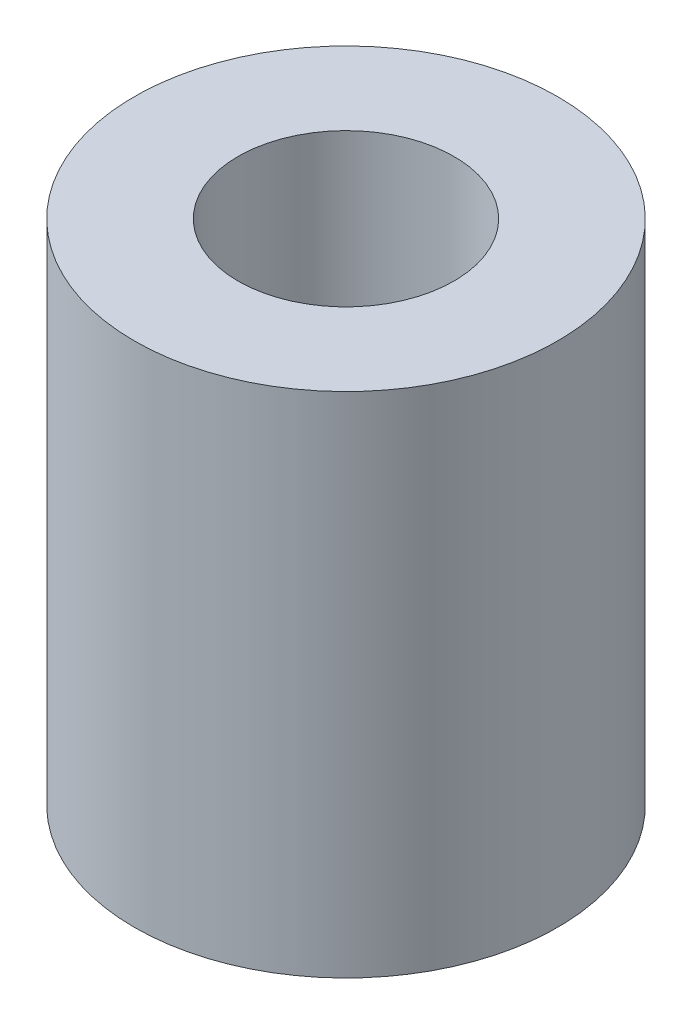
SolidWorks part; units mm, degrees
ref_plane "Front Plane" through (0, 0, 0) normal (0, 0, 1) x (1, 0, 0)
ref_plane "Top Plane" through (0, 0, 0) normal (0, 1, 0) x (1, 0, 0)
ref_plane "Right Plane" through (0, 0, 0) normal (1, 0, 0) x (0, 0, -1)
sketch "Sketch1" plane through (0, 0, 0) normal (0, 1, 0) x (1, 0, 0)
  circle A0 centre (0, 0) radius 7.9375
  dimension "D1" = 15.875
extrude "Boss-Extrude1" add sketch "Sketch1" along normal blind 19.05
sketch "Sketch2" plane through (0, 19.05, 0) normal (0, 1, 0) x (1, 0, 0)
  circle A0 centre (0, 0) radius 4
  dimension "D1" = 8
sketch "Sketch3" plane through (0, 19.05, 0) normal (0, 1, 0) x (1, 0, 0)
  circle A0 centre (0, 0) radius 4.05
  dimension "D1" = 8.1
extrude "Cut-Extrude2" cut sketch "Sketch3" against normal through all
